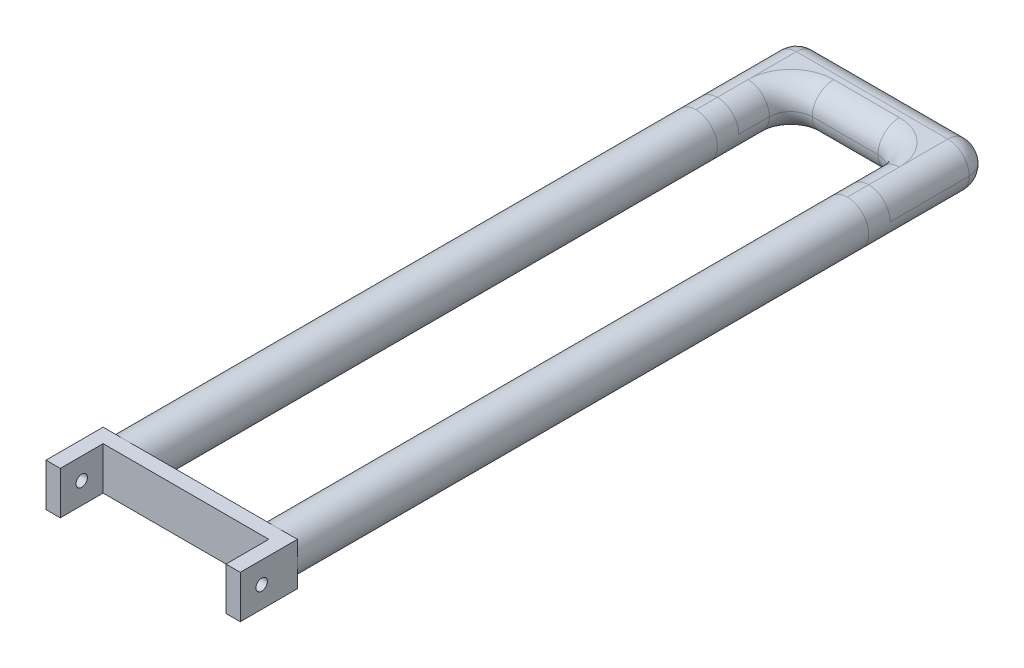
SolidWorks part; units mm, degrees
ref_plane "Front Plane" through (0, 0, 0) normal (0, 0, 1) x (1, 0, 0)
ref_plane "Top Plane" through (0, 0, 0) normal (0, 1, 0) x (1, 0, 0)
ref_plane "Right Plane" through (0, 0, 0) normal (1, 0, 0) x (0, 0, -1)
sketch "Sketch1" plane through (0, 0, 0) normal (0, 0, 1) x (1, 0, 0)
  line L1 (-86.36, -19.05) -> (86.36, -19.05)
  line L2 (-86.36, -19.05) -> (-86.36, 19.05)
  line L3 (-86.36, 19.05) -> (86.36, 19.05)
  line L4 (86.36, -19.05) -> (86.36, 19.05)
  line L5 (-86.36, -19.05) -> (86.36, 19.05) construction
  line L6 (-86.36, 19.05) -> (86.36, -19.05) construction
  point P0 (0, 0)
  dimension "D1" = 172.72
  dimension "D2" = 38.1
extrude "Boss-Extrude1" add sketch "Sketch1" along normal blind 12.7
sketch "Sketch2" plane through (0, 0, 12.7) normal (0, 0, 1) x (1, 0, 0)
  line L0 (-86.36, -19.05) -> (86.36, -19.05) construction
  line L1 (-86.36, 19.05) -> (-73.66, 19.05)
  line L2 (-86.36, 19.05) -> (-86.36, -19.05)
  line L3 (-86.36, -19.05) -> (-73.66, -19.05)
  line L4 (-73.66, 19.05) -> (-73.66, -19.05)
  line L6 (86.36, 19.05) -> (73.66, 19.05)
  line L7 (86.36, 19.05) -> (86.36, -19.05)
  line L8 (86.36, -19.05) -> (73.66, -19.05)
  line L9 (73.66, 19.05) -> (73.66, -19.05)
  dimension "D1" = 12.7
  dimension "D2" = 12.7
extrude "Boss-Extrude2" add sketch "Sketch2" along normal blind 38.1
sketch "Sketch3" plane through (0, 0, 0) normal (0, 0, -1) x (-1, 0, 0)
  line L0 (-86.36, -19.05) -> (-86.36, 19.05) construction
  line L1 (86.36, 19.05) -> (86.36, -19.05) construction
  circle A0 centre (-67.31, 0) radius 19.05
  circle A1 centre (67.31, 0) radius 19.05
  point P6 (45.7872, 0)
  point P9 (-66.89, 0)
  dimension "D3" = 38.1
  dimension "D1" = 19.05
  dimension "D2" = 19.05
extrude "Boss-Extrude3" add sketch "Sketch3" along normal blind 508
sketch "Sketch4" plane through (0, 0, 0) normal (0, 1, 0) x (1, 0, 0)
  line L1 (-86.36, 616.3882) -> (86.36, 616.3882)
  line L2 (-86.36, 616.3882) -> (-86.36, 573.3525)
  line L3 (-48.26, 573.3525) -> (48.26, 573.3525)
  line L4 (86.36, 616.3882) -> (86.36, 573.3525)
  line L8 (-86.36, 573.3525) -> (-86.36, 508)
  line L9 (-86.36, 508) -> (-48.26, 508)
  line L10 (-48.26, 573.3525) -> (-48.26, 508)
  line L12 (86.36, 573.3525) -> (86.36, 508)
  line L13 (86.36, 508) -> (48.26, 508)
  line L14 (48.26, 573.3525) -> (48.26, 508)
  point P0 (0, 594.8704)
extrude "Boss-Extrude5" add sketch "Sketch4" along normal mid plane 38.1
fillet "Fillet3" radius 19.05 12 edges at (0, 19.05, -573.3525) (0, -19.05, -573.3525) (48.26, 19.05, -540.6763) (48.26, -19.05, -540.6763) (-48.26, 19.05, -540.6763) (-48.26, -19.05, -540.6763) (-86.36, 19.05, -562.1941) (-86.36, -19.05, -562.1941) (86.36, 19.05, -562.1941) (86.36, -19.05, -562.1941) (0, 19.05, -616.3882) (0, -19.05, -616.3882)
sketch "Sketch5" plane through (-73.66, 0, 0) normal (1, 0, 0) x (0, 0, -1)
  circle A0 centre (-31.75, 0) radius 5.08
  dimension "D1" = 10.16
extrude "Cut-Extrude1" cut sketch "Sketch5" against normal through all both and the other way through all
